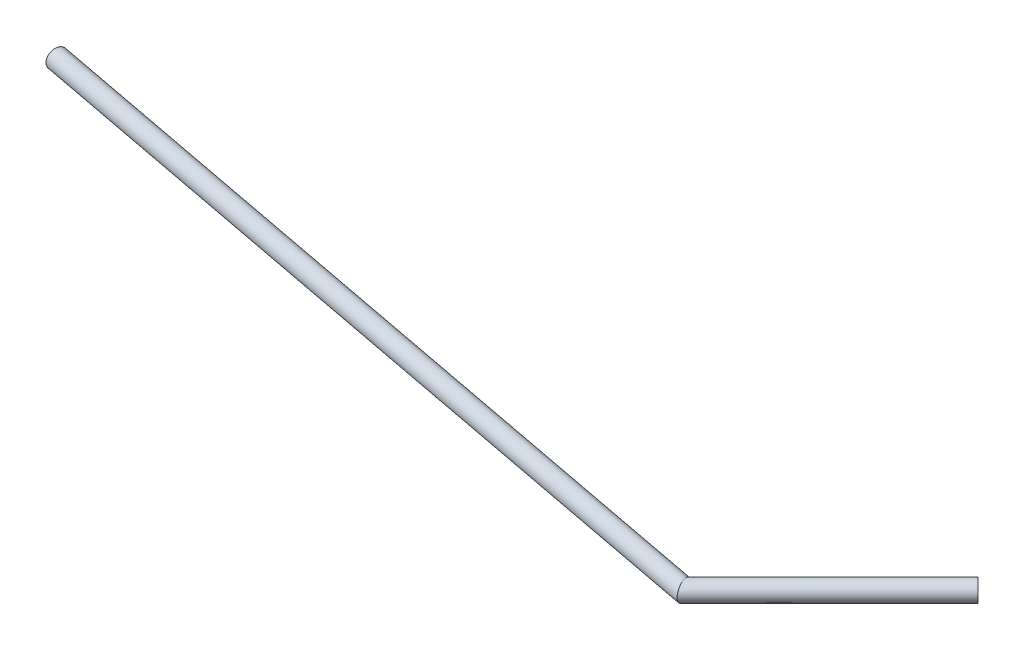
SolidWorks part; units mm, degrees
ref_plane "Front Plane" through (0, 0, 0) normal (0, 0, 1) x (1, 0, 0)
ref_plane "Top Plane" through (0, 0, 0) normal (0, 1, 0) x (1, 0, 0)
ref_plane "Right Plane" through (0, 0, 0) normal (1, 0, 0) x (0, 0, -1)
sketch "Sketch1" plane through (0, 0, 0) normal (0, 1, 0) x (1, 0, 0)
  line L0 (-470, 0) -> (470, 0) construction
  line L1 (470, 0) -> (320, -150)
  line L2 (-470, 0) -> (320, -150)
  point P3 (0, 0)
  dimension "D1" = 940
  dimension "D2" = 45
  dimension "D3" = 150
ref_plane "Plane1" through (-470, 0, 0) normal (0.9824, 0, 0.1865) x (0.1865, 0, -0.9824)
sketch "Sketch2" plane through (-470, 0, 0) normal (0.9824, 0, 0.1865) x (0.1865, 0, -0.9824)
  line L0 (0, 0) -> (175.3482, 0) construction
  line L1 (175.3482, 0) -> (0, 0) construction
  circle A0 centre (0, 0) radius 9.525
  dimension "D1" = 19.05
sweep "Sweep-Thin1" add profiles "Sketch2" path "Sketch1" parameters "D1"=1
